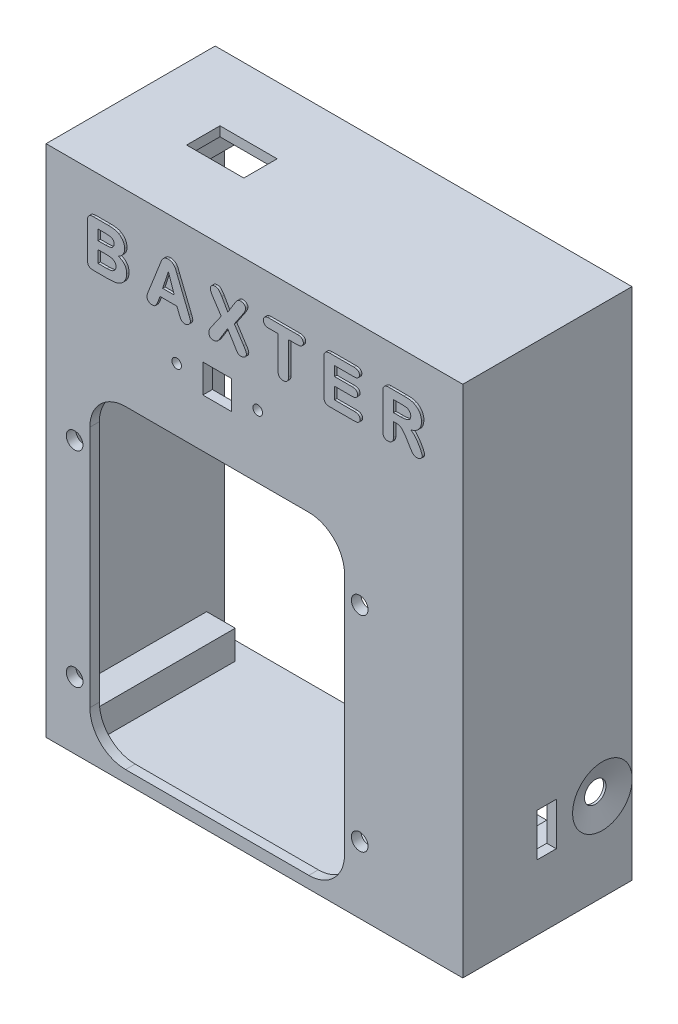
SolidWorks part; units mm, degrees
ref_plane "Front Plane" through (0, 0, 0) normal (0, 0, 1) x (1, 0, 0)
ref_plane "Top Plane" through (0, 0, 0) normal (0, 1, 0) x (1, 0, 0)
ref_plane "Right Plane" through (0, 0, 0) normal (1, 0, 0) x (0, 0, -1)
sketch "Sketch1" plane through (0, 0, 0) normal (0, 0, 1) x (1, 0, 0)
  line L0 (51.5441, -13.3108) -> (51.5441, -21.3108) construction
  line L1 (-35.915, -35.49) -> (51.5441, -35.49)
  line L2 (-35.915, -35.49) -> (-35.915, 72.421)
  line L3 (-35.915, 72.421) -> (51.5441, 72.421)
  line L4 (51.5441, -35.49) -> (51.5441, 72.421)
  line L6 (46.5772, 69.421) -> (21.5772, 69.421) construction
  line L7 (-19.2233, -32.49) -> (19.2233, -32.49) construction
  line L8 (-32.915, -24.6959) -> (-32.915, -18.3041) construction
  line L9 (26.2233, 25.49) -> (26.2233, -25.49) construction
  line L10 (-19.2233, 32.49) -> (19.2233, 32.49) construction
  line L11 (-26.2233, 25.49) -> (-26.2233, -25.49) construction
  line L12 (-19.2233, -32.49) -> (19.2233, -32.49) construction
  line L13 (26.2233, 25.49) -> (26.2233, -25.49) construction
  line L14 (-19.2233, 32.49) -> (19.2233, 32.49) construction
  line L15 (-26.2233, 25.49) -> (-26.2233, -25.49) construction
  line L16 (-2.5, 43.6921) -> (2.5, 43.6921) construction
  line L17 (-2.5, 48.6921) -> (-2.5, 43.6921) construction
  line L18 (2.5, 48.6921) -> (-2.5, 48.6921) construction
  line L19 (2.5, 43.6921) -> (2.5, 48.6921) construction
  line L20 (-2.5, 43.6921) -> (2.5, 43.6921) construction
  line L21 (-2.5, 48.6921) -> (-2.5, 43.6921) construction
  line L22 (2.5, 48.6921) -> (-2.5, 48.6921) construction
  line L23 (2.5, 43.6921) -> (2.5, 48.6921) construction
  line L24 (3, 49.1921) -> (-3, 49.1921)
  line L25 (-3, 49.1921) -> (-3, 43.1921)
  line L26 (-3, 43.1921) -> (3, 43.1921)
  line L27 (3, 43.1921) -> (3, 49.1921)
  line L28 (-19.2233, 32.99) -> (19.2233, 32.99)
  line L29 (26.7233, 25.49) -> (26.7233, -25.49)
  line L30 (-19.2233, -32.99) -> (19.2233, -32.99)
  line L31 (-26.7233, 25.49) -> (-26.7233, -25.49)
  circle A0 centre (29.915, 21.5) radius 1.6 construction
  circle A1 centre (29.915, -21.5) radius 1.6 construction
  circle A2 centre (-29.915, -21.5) radius 1.6 construction
  circle A3 centre (-29.915, 21.5) radius 1.6 construction
  arc A4 (-26.2233, -25.49) -> (-19.2233, -32.49) centre (-19.2233, -25.49) ccw construction
  arc A5 (19.2233, -32.49) -> (26.2233, -25.49) centre (19.2233, -25.49) ccw construction
  arc A6 (26.2233, 25.49) -> (19.2233, 32.49) centre (19.2233, 25.49) ccw construction
  arc A7 (-19.2233, 32.49) -> (-26.2233, 25.49) centre (-19.2233, 25.49) ccw construction
  circle A8 centre (29.915, 21.5) radius 1.6 construction
  circle A9 centre (29.915, -21.5) radius 1.6 construction
  circle A10 centre (-29.915, -21.5) radius 1.6 construction
  circle A11 centre (-29.915, 21.5) radius 1.6 construction
  arc A12 (-26.2233, -25.49) -> (-19.2233, -32.49) centre (-19.2233, -25.49) ccw construction
  arc A13 (19.2233, -32.49) -> (26.2233, -25.49) centre (19.2233, -25.49) ccw construction
  arc A14 (26.2233, 25.49) -> (19.2233, 32.49) centre (19.2233, 25.49) ccw construction
  arc A15 (-19.2233, 32.49) -> (-26.2233, 25.49) centre (-19.2233, 25.49) ccw construction
  arc A16 (26.7233, 25.49) -> (19.2233, 32.99) centre (19.2233, 25.49) ccw
  arc A17 (19.2233, -32.99) -> (26.7233, -25.49) centre (19.2233, -25.49) ccw
  arc A18 (-26.7233, -25.49) -> (-19.2233, -32.99) centre (-19.2233, -25.49) ccw
  arc A19 (-19.2233, 32.99) -> (-26.7233, 25.49) centre (-19.2233, 25.49) ccw
  circle A20 centre (-29.915, 21.5) radius 1.75
  circle A21 centre (-29.915, -21.5) radius 1.75
  circle A22 centre (29.915, -21.5) radius 1.75
  circle A23 centre (29.915, 21.5) radius 1.75
  circle A24 centre (8.5, 46.1921) radius 1 construction
  circle A25 centre (-8.5, 46.1921) radius 1 construction
  circle A26 centre (8.5, 46.1921) radius 1
  circle A27 centre (-8.5, 46.1921) radius 1
  dimension "D6" = 3.5
  dimension "D7" = 3.5
  dimension "D8" = 3.5
  dimension "D9" = 3.5
  dimension "D1" = 3
  dimension "D2" = 3
  dimension "D3" = 3
  dimension "D4" = 0.5
  dimension "D5" = 0.5
extrude "Boss-Extrude1" add sketch "Sketch1" against normal blind 2
sketch "Sketch2" plane through (0, 0, 0) normal (0, 0, 1) x (1, 0, 0)
  line L0 (-35.915, 54.8651) -> (51.5441, 54.8651) construction
  line L1 (-35.915, 72.421) -> (-35.915, -35.49) construction
  line L2 (51.5441, -35.49) -> (51.5441, 72.421) construction
  text T0 "<b>BAXTER</b>" font "Arial Rounded MT Bold" height 10
extrude "Boss-Extrude2" add sketch "Sketch2" along normal blind 0.5
sketch "Sketch3" plane through (0, 0, -2) normal (0, 0, -1) x (-1, 0, 0)
  line L12 (33.915, -33.49) -> (33.915, 70.421)
  line L13 (33.915, 70.421) -> (-49.5441, 70.421)
  line L14 (-49.5441, 70.421) -> (-49.5441, -33.49)
  line L15 (-49.5441, -33.49) -> (33.915, -33.49)
  line L16 (33.915, -33.49) -> (33.915, 70.421)
  line L17 (33.915, 70.421) -> (-49.5441, 70.421)
  line L18 (-49.5441, 70.421) -> (-49.5441, -33.49)
  line L19 (-49.5441, -33.49) -> (33.915, -33.49)
  line L20 (35.915, -35.49) -> (35.915, 72.421)
  line L21 (35.915, 72.421) -> (-51.5441, 72.421)
  line L22 (-51.5441, 72.421) -> (-51.5441, -35.49)
  line L23 (-51.5441, -35.49) -> (35.915, -35.49)
  line L24 (35.915, -35.49) -> (35.915, 72.421)
  line L25 (35.915, 72.421) -> (-51.5441, 72.421)
  line L26 (-51.5441, 72.421) -> (-51.5441, -35.49)
  line L27 (-51.5441, -35.49) -> (35.915, -35.49)
  dimension "D1" = 2
  dimension "D2" = 0
extrude "Boss-Extrude3" add sketch "Sketch3" along normal blind 33.5
sketch "Sketch4" plane through (0, 72.421, 0) normal (0, 1, 0) x (1, 0, 0)
  line L0 (-35.915, 35.5) -> (-35.915, 0) construction
  line L1 (-8.915, 21.5) -> (-20.915, 21.5)
  line L2 (-8.915, 21.5) -> (-8.915, 14.5)
  line L3 (-8.915, 14.5) -> (-20.915, 14.5)
  line L4 (-20.915, 21.5) -> (-20.915, 14.5)
  line L5 (-35.915, 35.5) -> (51.5441, 35.5) construction
  dimension "D1" = 12
  dimension "D2" = 7
  dimension "D3" = 15
  dimension "D4" = 14
extrude "Cut-Extrude1" cut sketch "Sketch4" against normal up to next
sketch "Sketch5" plane through (51.5441, 0, 0) normal (1, 0, 0) x (0, 0, -1)
  line L0 (15.6238, -21.8108) -> (15.6238, -12.8108)
  line L1 (16.1238, -21.3108) -> (19.1238, -21.3108) construction
  line L2 (16.1238, -21.3108) -> (16.1238, -13.3108) construction
  line L3 (16.1238, -13.3108) -> (19.1238, -13.3108) construction
  line L4 (19.1238, -21.3108) -> (19.1238, -13.3108) construction
  line L5 (15.6238, -12.8108) -> (19.6238, -12.8108)
  line L6 (19.6238, -21.8108) -> (19.6238, -12.8108)
  line L7 (15.6238, -21.8108) -> (19.6238, -21.8108)
  dimension "D1" = 0.5
extrude "Cut-Extrude2" cut sketch "Sketch5" against normal up to next
sketch "Sketch6" plane through (49.5441, 0, 0) normal (-1, 0, 0) x (0, 0, 1)
  line L1 (-27.7493, -15.4355) -> (-30.8497, -15.4355)
  line L2 (-27.7493, -15.4355) -> (-27.7493, -18.703)
  line L3 (-27.7493, -18.703) -> (-30.8497, -18.703)
  line L4 (-30.8497, -15.4355) -> (-30.8497, -18.703)
  point P4 (-30.8497, -15.4355)
  point P5 (-27.7493, -18.703)
extrude "Cut-Extrude3" cut sketch "Sketch6" against normal up to next
sketch "Sketch7" plane through (51.5441, 0, 0) normal (1, 0, 0) x (0, 0, -1)
  line L0 (30.8497, -18.703) -> (27.7493, -15.4355) construction
  circle A0 centre (29.2995, -17.0692) radius 2.2522
extrude "Cut-Extrude4" cut sketch "Sketch7" against normal up to next
chamfer "Chamfer1" distance 4 distance2 1.5 1 edges at (51.5441, -17.0692, -31.5517)
sketch "Sketch8" plane through (0, 0, -2) normal (0, 0, -1) x (-1, 0, 0)
  line L0 (-49.5441, -33.49) -> (33.915, -33.49) construction
  line L1 (-43.0772, -33.49) -> (-49.5441, -33.49)
  line L2 (-43.0772, -33.49) -> (-43.0772, -24.079)
  line L3 (-43.0772, -24.079) -> (-49.5441, -24.079)
  line L4 (-49.5441, -33.49) -> (-49.5441, -24.079)
  line L5 (-49.5441, 70.421) -> (-49.5441, -33.49) construction
  line L6 (33.915, 70.421) -> (-49.5441, 70.421) construction
  line L7 (-49.5441, 70.421) -> (-43.0772, 70.421)
  line L8 (-49.5441, 70.421) -> (-49.5441, 63.921)
  line L9 (-49.5441, 63.921) -> (-47.0772, 63.921)
  line L10 (-43.0772, 70.421) -> (-43.0772, 67.921)
  line L11 (33.915, -33.49) -> (33.915, 70.421) construction
  line L13 (25.915, 70.421) -> (33.915, 70.421)
  line L14 (25.915, 70.421) -> (25.915, 62.421)
  line L15 (25.915, 62.421) -> (33.915, 62.421)
  line L16 (33.915, 70.421) -> (33.915, 62.421)
  line L17 (27.915, -33.49) -> (33.915, -33.49)
  line L18 (27.915, -33.49) -> (27.915, -27.49)
  line L19 (27.915, -27.49) -> (33.915, -27.49)
  line L20 (33.915, -33.49) -> (33.915, -27.49)
  circle A0 centre (-46.5772, -27.579) radius 1.5
  circle A1 centre (-46.5772, 67.421) radius 1.5
  arc A2 (-47.0772, 63.921) -> (-43.0772, 67.921) centre (-47.0772, 67.921) ccw
  circle A3 centre (29.915, 66.421) radius 1.5
  circle A4 centre (30.915, -30.49) radius 1.5
  dimension "D2" = 3.5
  dimension "D3" = 3
  dimension "D4" = 3
  dimension "D7" = 4
  dimension "D8" = 3
  dimension "D12" = 4
  dimension "D13" = 3
  dimension "D14" = 3
  dimension "D15" = 3
  dimension "D16" = 3
  dimension "D1" = 3.5
  dimension "D5" = 3.5
  dimension "D6" = 3.5
  dimension "D9" = 4
  dimension "D10" = 4
  dimension "D11" = 4
  dimension "D17" = 3
extrude "Boss-Extrude4" add sketch "Sketch8" along normal up to vertex (29.7044 mm away)
chamfer "Chamfer2" distance 0.5 angle 45 4 edges at (45.0772, -27.579, -31.7044) (45.0772, 67.421, -31.7044) (-32.415, -30.49, -31.7044) (-31.415, 66.421, -31.7044)
